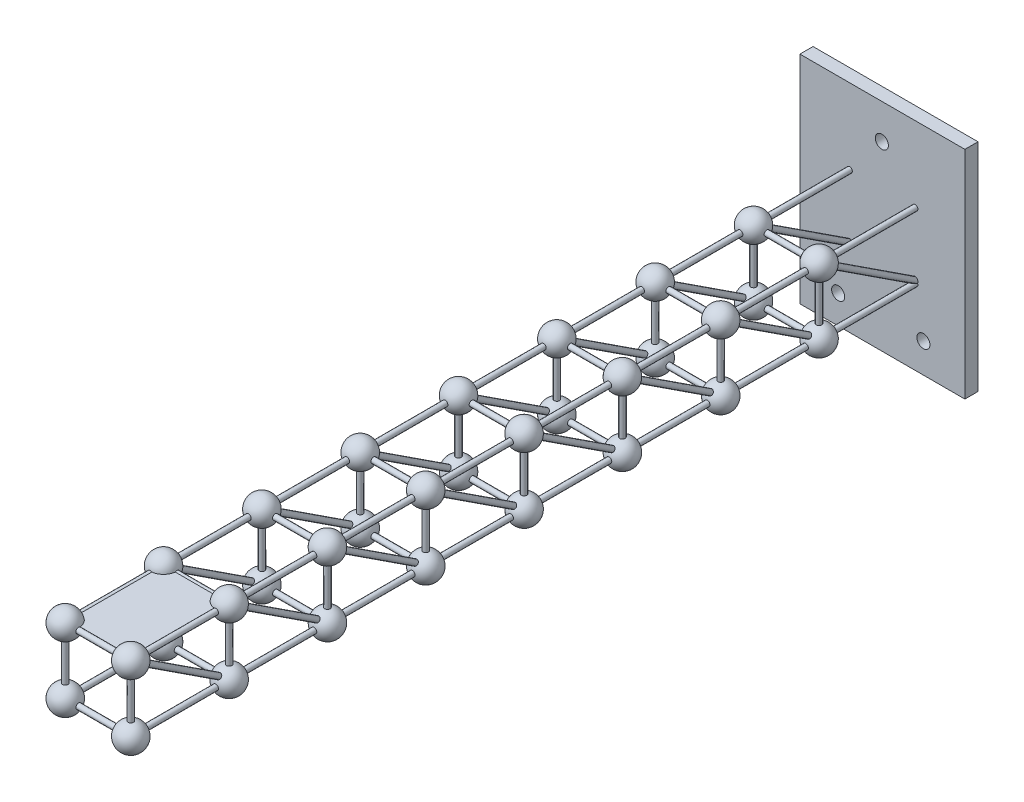
SolidWorks part; units mm, degrees
ref_plane "Front Plane" through (0, 0, 0) normal (0, 0, 1) x (1, 0, 0)
ref_plane "Top Plane" through (0, 0, 0) normal (0, 1, 0) x (1, 0, 0)
ref_plane "Right Plane" through (0, 0, 0) normal (1, 0, 0) x (0, 0, -1)
sketch "Sketch1" plane through (0, 0, 0) normal (0, 0, 1) x (1, 0, 0)
  line L1 (0, 0) -> (151, 0)
  line L2 (0, 0) -> (0, -198)
  line L3 (0, -198) -> (151, -198)
  line L4 (151, 0) -> (151, -198)
  dimension "D1" = 198
  dimension "D2" = 151
extrude "Boss-Extrude1" add sketch "Sketch1" along normal blind 12
sketch "Sketch2" plane through (0, 0, 12) normal (0, 0, 1) x (1, 0, 0)
  line L0 (151, -198) -> (151, 0) construction
  circle A0 centre (75, -32) radius 6
  circle A1 centre (35, -172) radius 6
  circle A2 centre (113, -171) radius 6
  dimension "D1" = 35
  dimension "D7" = 12
  dimension "D2" = 26
  dimension "D3" = 38
  dimension "D4" = 27
  dimension "D5" = 32
  dimension "D6" = 75
extrude "Cut-Extrude1" cut sketch "Sketch2" against normal blind 12
sketch "Sketch3" plane through (0, 0, 0) normal (0, 0, 1) x (1, 0, 0)
  line L0 (75.5, 0) -> (75.5, -198) construction
  line L2 (151, 0) -> (0, 0) construction
  line L3 (0, -198) -> (151, -198) construction
  line L4 (0, -99) -> (151, -99) construction
  line L5 (0, 0) -> (0, -198) construction
  line L6 (151, -198) -> (151, 0) construction
  circle A0 centre (45.5, -129) radius 2.5
  circle A1 centre (105.5, -129) radius 2.5
  circle A2 centre (105.5, -69) radius 2.5
  circle A3 centre (45.5, -69) radius 2.5
  dimension "D1" = 5
  dimension "D2" = 30
  dimension "D3" = 30
extrude "Boss-Extrude2" add sketch "Sketch3" along normal blind 100
ref_plane "Plane2" through (0, 0, 100) normal (0, 0, 1) x (1, 0, 0)
sketch "Sketch5" plane through (0, 0, 100) normal (0, 0, 1) x (1, 0, 0)
  line L0 (33, -69) -> (58, -69)
  line L1 (75.5, 0) -> (75.5, -198) construction
  line L2 (151, 0) -> (0, 0) construction
  line L3 (0, -198) -> (151, -198) construction
  line L4 (0, -99) -> (151, -99) construction
  line L5 (0, 0) -> (0, -198) construction
  line L6 (151, -198) -> (151, 0) construction
  arc A0 (58, -69) -> (33, -69) centre (45.5, -69) ccw
  dimension "D1" = 12.5
revolve "Revolve4" add sketch "Sketch5" angle 360 about L0
pattern_linear "LPattern2" count 2 spacing 60 along (1, 0, 0) count 2 spacing 60 along (0, -1, 0) of "Revolve4"
ref_plane "Plane3" through (0, -70, 0) normal (0, -1, 0) x (-1, 0, 0)
sketch "Sketch6" plane through (0, -70, 0) normal (0, -1, 0) x (-1, 0, 0)
  line L0 (-105.5, -12) -> (-105.5, -146.585) construction
  line L1 (-108, -12) -> (-103, -12) construction
  line L2 (-45.5, -12) -> (-45.5, -146.585) construction
  line L3 (-48, -12) -> (-43, -12) construction
  line L4 (-118, -100) -> (-33, -100) construction
  line L6 (-108, -87.7526) -> (-103, -87.7526) construction
  line L7 (-75.5, -130.3466) -> (-75.5, -83.717) construction
  arc A0 (-108, -87.7526) -> (-103, -87.7526) centre (-105.5, -100) ccw construction
  arc A1 (-48, -87.7526) -> (-43, -87.7526) centre (-45.5, -100) ccw construction
  circle A2 centre (-105.5, -100.0026) radius 2.5
  circle A3 centre (-45.5, -100.0026) radius 2.5
  dimension "D1" = 5
  dimension "D2" = 12.25
extrude "Boss-Extrude3" add sketch "Sketch6" along normal blind 60
ref_plane "Plane8" through (45.5, 0, 0) normal (1, 0, 0) x (0, 0, -1)
sketch "Sketch7" plane through (45.5, 0, 0) normal (1, 0, 0) x (0, 0, -1)
  line L0 (-100, -56.5) -> (-100, -141.5) construction
  line L2 (-87.7526, -126.5) -> (-87.7526, -131.5) construction
  line L3 (-12, -129) -> (-134.9847, -129) construction
  line L4 (-12, -126.5) -> (-12, -131.5) construction
  line L5 (-12, -69) -> (-144.7985, -69) construction
  line L6 (-12, -66.5) -> (-12, -71.5) construction
  line L7 (-12, -99) -> (-166.9947, -99) construction
  line L8 (-12, 0) -> (-12, -198) construction
  arc A0 (-87.7526, -66.5) -> (-102.5025, -81.2469) centre (-100, -69) ccw construction
  arc A1 (-102.5025, -116.7531) -> (-87.7526, -131.5) centre (-100, -129) ccw construction
  circle A2 centre (-100.0026, -129) radius 2.5
  circle A3 centre (-100.0026, -69) radius 2.5
  dimension "D1" = 5
  dimension "D2" = 12.25
extrude "Boss-Extrude4" add sketch "Sketch7" along normal blind 60
sketch "Sketch8" plane through (0, 0, 0) normal (1, 0, 0) x (0, 0, -1)
  line L0 (-12, -69) -> (-149.8505, -69) construction
  line L1 (-12, -66.5) -> (-12, -71.5) construction
  line L2 (-100.0026, -116.7526) -> (-100.0026, -36.6347) construction
  line L3 (-102.5026, -116.7531) -> (-97.5026, -116.752) construction
  line L4 (-100.0026, -69) -> (-12, -126.5) construction
  point P8 (-100.0026, -69)
ref_plane "Plane9" through (0, -69, 100.0026) normal (0, -0.547, -0.8371) x (-1, 0, 0)
sketch "Sketch9" plane through (0, -69, 100.0026) normal (0, -0.547, -0.8371) x (-1, 0, 0)
  line L0 (0, 0) -> (-155.9018, 0) construction
  line L1 (-75.5, -2.5) -> (-75.5, 65.3283) construction
  line L2 (-93.2528, -2.5) -> (-57.7472, -2.5) construction
  line L3 (-45.5, 0) -> (-45.5, 56.6592) construction
  line L4 (-105.5, 0) -> (-105.5, 55.5989) construction
  circle A0 centre (-45.5, 0) radius 2.5
  circle A1 centre (-105.5, 0) radius 2.5
  dimension "D3" = 5
  dimension "D4" = 5
  dimension "D1" = 30
  dimension "D2" = 30
extrude "Boss-Extrude5" add sketch "Sketch9" along normal blind 115
pattern_linear "LPattern3" count 8 spacing 90 along (0, 0, 1) of "LPattern2", "Revolve4", "Boss-Extrude2", "Boss-Extrude5", "Boss-Extrude3", "Boss-Extrude4"
ref_plane "Plane15" through (0, -69, 0) normal (0, -1, 0) x (-1, 0, 0)
sketch "Sketch11" plane through (0, -69, 0) normal (0, -1, 0) x (-1, 0, 0)
  line L0 (-57.7474, -730.0026) -> (-133.9904, -730.0026) construction
  line L1 (-57.748, -727.5026) -> (-57.7469, -732.5026) construction
  line L2 (-105.5, -652.2474) -> (-105.5, -746.6944) construction
  line L3 (-103, -652.2474) -> (-108, -652.2474) construction
  line L4 (-93.2526, -640.0026) -> (-19.5273, -640.0026) construction
  line L5 (-93.2531, -642.5026) -> (-93.252, -637.5026) construction
  line L6 (-45.5, -717.7526) -> (-45.5, -634.982) construction
  line L7 (-48, -717.7526) -> (-43, -717.7526) construction
  line L9 (-45.5, -640.0026) -> (-105.5, -640.0026)
  line L10 (-45.5, -640.0026) -> (-45.5, -730.0026)
  line L11 (-45.5, -730.0026) -> (-105.5, -730.0026)
  line L12 (-105.5, -640.0026) -> (-105.5, -730.0026)
  point P16 (-105.5, -730.0026)
  point P17 (-45.5, -640.0026)
extrude "Boss-Extrude6" add sketch "Sketch11" along normal blind 2 and the other way blind 2 contours L10 L9 L12 L11
